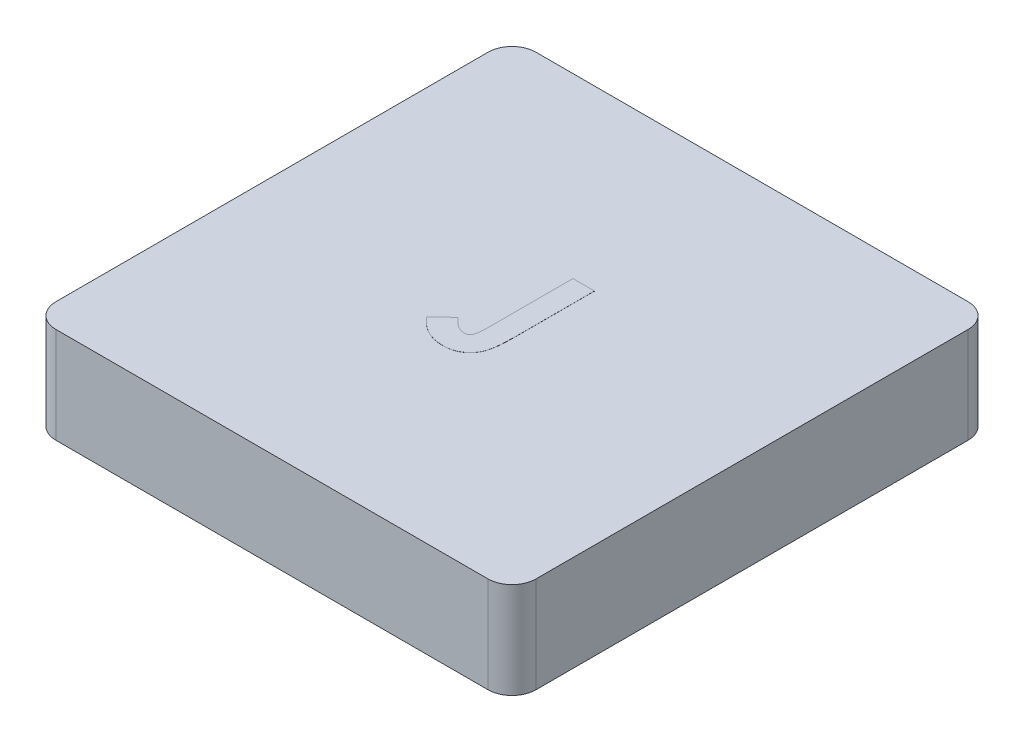
SolidWorks part; units mm, degrees
ref_plane "Front Plane" through (0, 0, 0) normal (0, 0, 1) x (1, 0, 0)
ref_plane "Top Plane" through (0, 0, 0) normal (0, 1, 0) x (1, 0, 0)
ref_plane "Right Plane" through (0, 0, 0) normal (1, 0, 0) x (0, 0, -1)
sketch "Sketch1" plane through (0, 0, 0) normal (0, 1, 0) x (1, 0, 0)
  line L0 (0, 0) -> (12.7, 0)
  line L1 (12.7, 0) -> (12.7, 12.7)
  line L2 (12.7, 12.7) -> (0, 12.7)
  line L3 (0, 12.7) -> (0, 0)
  dimension "D1" = 12.7
  dimension "D2" = 12.7
extrude "Boss-Extrude1" add sketch "Sketch1" along normal blind 2.54
fillet "Fillet1" radius 0.635 4 edges at (0, 1.27, -12.7) (12.7, 1.27, -12.7) (12.7, 1.27, 0) (0, 1.27, 0)
shell "Shell1" thickness 0.635 removed face at (6.35, 0, -6.35)
sketch "Sketch2" plane through (0, 1.905, 0) normal (0, -1, 0) x (-1, 0, 0)
  line L0 (-0.635, 6.35) -> (-12.065, 6.35) construction
  line L1 (-0.635, 12.065) -> (-0.635, 0.635) construction
  line L2 (-12.065, 0.635) -> (-12.065, 12.065) construction
  line L3 (-6.35, 0.635) -> (-6.35, 12.065) construction
  line L4 (-0.635, 0.635) -> (-12.065, 0.635) construction
  line L5 (-12.065, 12.065) -> (-0.635, 12.065) construction
  circle A0 centre (-6.35, 6.35) radius 2.54
  dimension "D1" = 5.08
extrude "Boss-Extrude2" add sketch "Sketch2" along normal up to surface (1.905 mm away) up to face at (6.35, 0, -6.35)
sketch "Sketch3" plane through (0, 2.54, 0) normal (0, 1, 0) x (1, 0, 0)
  line L0 (0, 12.065) -> (0, 0.635) construction
  line L1 (0.635, 0) -> (12.065, 0) construction
  text T0 "<b>J</b>"
  point P1 (0, 0)
  dimension "D1" = 5.1308
  dimension "D2" = 4.826
extrude "Boss-Extrude3" add sketch "Sketch3" along normal blind 0.0025
